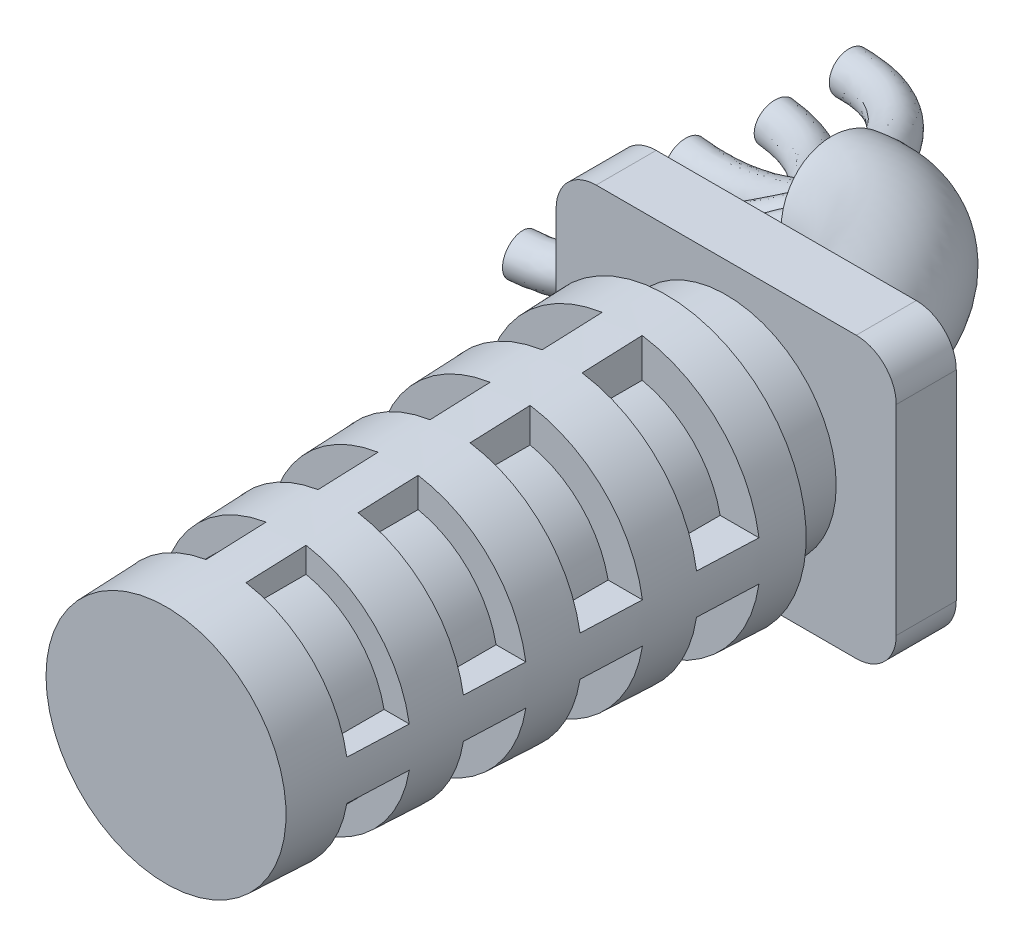
SolidWorks part; units mm, degrees
material "POLYURETHANE (11671)"
ref_plane "Front Plane" through (0, 0, 0) normal (0, 0, 1) x (1, 0, 0)
ref_plane "Top Plane" through (0, 0, 0) normal (0, 1, 0) x (1, 0, 0)
ref_plane "Right Plane" through (0, 0, 0) normal (1, 0, 0) x (0, 0, -1)
sketch "Sketch1" plane through (0, 0, 0) normal (0, 0, 1) x (1, 0, 0)
  line L1 (4.25, -3.5) -> (-4.25, -3.5)
  line L2 (4.25, -3.5) -> (4.25, 3.5)
  line L3 (4.25, 3.5) -> (-4.25, 3.5)
  line L4 (-4.25, -3.5) -> (-4.25, 3.5)
  line L5 (4.25, -3.5) -> (-4.25, 3.5) construction
  line L6 (4.25, 3.5) -> (-4.25, -3.5) construction
  circle A0 centre (0, 0) radius 1.8
  point P0 (0, 0)
  dimension "D3" = 3.6
  dimension "D1" = 8.5
  dimension "D2" = 7
extrude "Boss-Extrude1" add sketch "Sketch1" along normal blind 1.5
sketch "Sketch2" plane through (0, 0, 1.5) normal (0, 0, 1) x (1, 0, 0)
  circle A0 centre (0, 0) radius 2.75
  circle M5 centre (0, 0) radius 1.8
  dimension "D1" = 5.5
extrude "Boss-Extrude2" add sketch "Sketch2" along normal blind 1.5 contours A0 M5 region at (-2.6722, 0, 1.5)
sketch "Sketch4" plane through (0, 0, 0) normal (0, 1, 0) x (1, 0, 0)
  line L0 (-1.8, -3) -> (-3.5, -3)
  line L1 (-3.5, -3) -> (-3, -15.5)
  line L2 (-3, -15.5) -> (-1.8, -15.5)
  line L3 (-1.8, -15.5) -> (-1.8, -3)
  line L4 (0, 0) -> (0, -4.1714) construction
  line L5 (4.25, 0) -> (-4.25, 0) construction
  dimension "D1" = 7
  dimension "D2" = 6
  dimension "D3" = 15.5
revolve "Revolve1" add sketch "Sketch4" angle 360 about L4
fillet "Fillet1" radius 1 4 edges at (4.25, -3.5, 0.75) (-4.25, -3.5, 0.75) (-4.25, 3.5, 0.75) (4.25, 3.5, 0.75)
sketch "Sketch5" plane through (0, 0, 15.5) normal (0, 0, 1) x (1, 0, 0)
  line L0 (-0.5, 2.4495) -> (-0.5, 3.7498)
  line L1 (-0.5, 3.7498) -> (-4.5796, 3.7498)
  line L2 (-4.5796, 3.7498) -> (-4.5796, 0.5)
  line L3 (-4.5796, 0.5) -> (-2.4495, 0.5)
  line L4 (-0.8846, 0) -> (0, 0) construction
  line L5 (0, 0) -> (0, 1.276) construction
  line L6 (0.5, 4.5796) -> (0.5, 2.4495)
  line L7 (3.7498, 4.5796) -> (0.5, 4.5796)
  line L8 (3.7498, 0.5) -> (3.7498, 4.5796)
  line L9 (2.4495, 0.5) -> (3.7498, 0.5)
  line L10 (4.5796, -0.5) -> (2.4495, -0.5)
  line L11 (4.5796, -3.7498) -> (4.5796, -0.5)
  line L12 (0.5, -3.7498) -> (4.5796, -3.7498)
  line L13 (0.5, -2.4495) -> (0.5, -3.7498)
  line L14 (-0.5, -4.5796) -> (-0.5, -2.4495)
  line L15 (-3.7498, -4.5796) -> (-0.5, -4.5796)
  line L16 (-3.7498, -0.5) -> (-3.7498, -4.5796)
  line L17 (-2.4495, -0.5) -> (-3.7498, -0.5)
  circle A0 centre (0, 0) radius 2.5
  circle M8 centre (0, 0) radius 3
  dimension "D1" = 5
  dimension "D2" = 1
  dimension "D3" = 1
  dimension "D4" = 4
extrude "Cut-Extrude1" cut sketch "Sketch5" against normal blind 1.5 from offset 1.5 contours L2 L3 L0 L1 M8 | L9 L8 L7 L6 M8 | L13 L12 L11 L10 M8 | L17 L16 L15 L14 M8 | A0 L0 L3 M8 | A0 L17 L14 M8 | A0 L13 L10 M8 | A0 L9 L6 M8 region at (-1.8353, 1.8353, 15.5) region at (-3.0488, 2.4325, 15.5) region at (1.8353, 1.8353, 15.5) region at (2.4325, 3.0488, 15.5) region at (-1.8353, -1.8353, 15.5) region at (-2.4325, -3.0488, 15.5) region at (1.8353, -1.8353, 15.5) region at (3.0488, -2.4325, 15.5) offset against normal yes
pattern_linear "LPattern1" count 4 spacing 2.8 along (0, 0, -1) of "Cut-Extrude1"
sketch "Sketch6" plane through (0, 0, 0) normal (0, 0, -1) x (-1, 0, 0)
  circle A0 centre (0, 0) radius 1.8
extrude "Boss-Extrude3" add sketch "Sketch6" against normal through all
sketch3d "3DSketch1"
  spline S0 degree 3 poles (0, 0, 0) (-0.1483, -0.1183, -3.047) (-2.8532, -1.3266, -6.202) (-4.7664, -1.7486, -6.2609) knots 0 0 0 0 1 1 1 1
sweep "MainCable" add path "3DSketch1" circular profile diameter 3.1 parameters "D3"=3.1
sketch3d "3DSketch2"
  spline S0 degree 3 poles (-4.4291, -1.7486, -6.5982) (-5.9632, -2.3121, -7.2055) (-6.3645, -2.989, -10.6349) (-9.0964, -3.0693, -10.6818) knots 0 0 0 0 1 1 1 1
sweep "PWR" add path "3DSketch2" circular profile diameter 1 parameters "D3"=1
sketch3d "3DSketch3"
  spline S0 degree 3 poles (-4.7664, -1.7486, -6.2609) (-6.1965, -2.2557, -6.4867) (-7.1179, -3.1376, -8.541) (-8.9348, -3.0548, -8.6683) knots 0 0 0 0 1 1 1 1
sweep "DM" add path "3DSketch3" circular profile diameter 1 parameters "D3"=1
sketch3d "3DSketch4"
  spline S0 degree 3 poles (-4.7664, -1.7486, -6.2609) (-6.1912, -2.3178, -6.4005) (-7.2679, -3.1344, -6.5924) (-9.2016, -3.0288, -6.6837) knots 0 0 0 0 1 1 1 1
sweep "DP" add path "3DSketch4" circular profile diameter 1 parameters "D3"=1
sketch3d "3DSketch5"
  spline S0 degree 3 poles (-4.7664, -1.7486, -6.2609) (-6.2596, -2.403, -5.9887) (-6.8923, -3.0488, -4.6952) (-9.1832, -3.0226, -4.667) knots 0 0 0 0 1 1 1 1
sweep "GND" add path "3DSketch5" circular profile diameter 1 parameters "D3"=1
sketch3d "3DSketch6"
  spline S0 degree 3 poles (-4.5347, -1.7411, -5.7789) (-6.3166, -2.266, -4.7311) (-6.5831, -3.0529, -2.8014) (-9.1901, -2.996, -2.5489) knots 0 0 0 0 1 1 1 1
sweep "Shield" add path "3DSketch6" circular profile diameter 1 parameters "D3"=1
